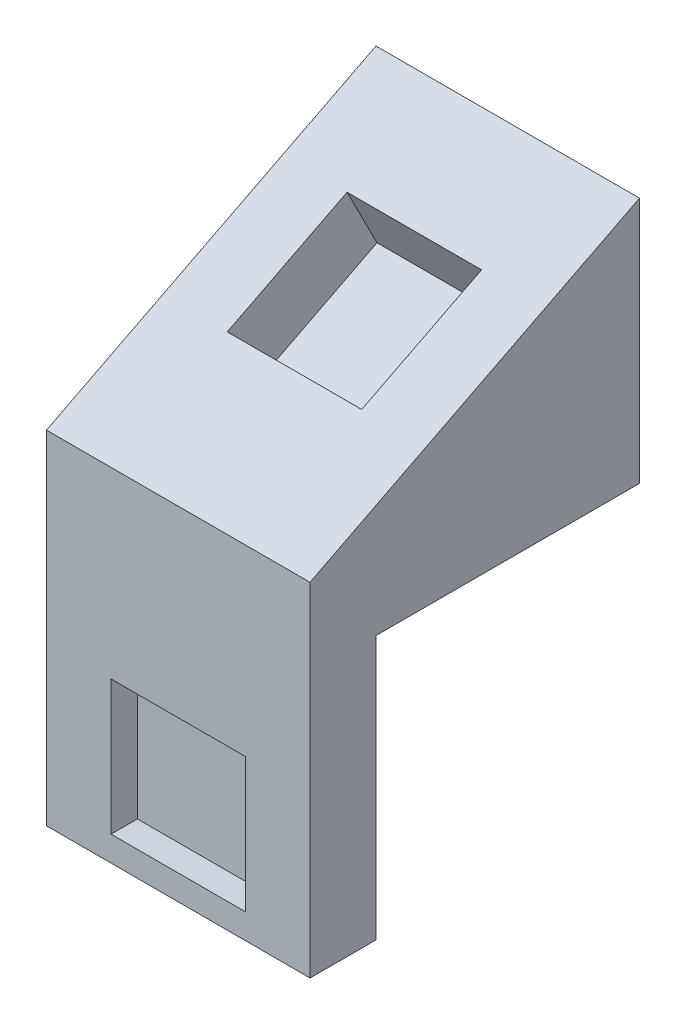
SolidWorks part; units mm, degrees
ref_plane "Płaszczyzna przednia" through (0, 0, 0) normal (0, 0, 1) x (1, 0, 0)
ref_plane "Płaszczyzna górna" through (0, 0, 0) normal (0, 1, 0) x (1, 0, 0)
ref_plane "Płaszczyzna prawa" through (0, 0, 0) normal (1, 0, 0) x (0, 0, -1)
sketch "Szkic1" plane through (0, 0, 0) normal (0, 0, 1) x (1, 0, 0)
  line L1 (-10, -13) -> (10, -13)
  line L2 (-10, -13) -> (-10, 13)
  line L3 (-10, 13) -> (10, 13)
  line L4 (10, -13) -> (10, 13)
  line L5 (-10, -13) -> (10, 13) construction
  line L6 (-10, 13) -> (10, -13) construction
  point P0 (0, 0)
  dimension "D1" = 26
  dimension "D2" = 20
extrude "Dodanie-wyciągnięcie1" add sketch "Szkic1" along normal blind 5
sketch "Szkic2" plane through (0, 0, 0) normal (0, 0, -1) x (-1, 0, 0)
  line L1 (10, 13) -> (-10, 13)
  line L2 (10, 13) -> (10, 7)
  line L3 (10, 7) -> (-10, 7)
  line L4 (-10, 13) -> (-10, 7)
  line L5 (-10, -13) -> (-10, 13) construction
  dimension "D1" = 6
  dimension "D2" = 20
extrude "Dodanie-wyciągnięcie2" add sketch "Szkic2" along normal blind 20
sketch "Szkic3" plane through (0, 0, 5) normal (0, 0, 1) x (1, 0, 0)
  line L0 (10, 13) -> (-10, 13) construction
  line L1 (-5.1, -11.1) -> (5.1, -11.1)
  line L2 (-5.1, -11.1) -> (-5.1, -0.9)
  line L3 (-5.1, -0.9) -> (5.1, -0.9)
  line L4 (5.1, -11.1) -> (5.1, -0.9)
  line L5 (-5.1, -11.1) -> (5.1, -0.9) construction
  line L6 (-5.1, -0.9) -> (5.1, -11.1) construction
  line L7 (-10, -13) -> (10, -13) construction
  point P0 (0, -6)
  point P7 (0, 13)
  dimension "D1" = 10.2
  dimension "D2" = 7
extrude "Wytnij-wyciągnięcie1" cut sketch "Szkic3" against normal blind 2
sketch "Szkic4" plane through (10, 0, 0) normal (1, 0, 0) x (0, 0, -1)
  line L0 (-5, 13) -> (20, 25.7381)
  line L1 (-5, 13) -> (20, 13) construction
  line L2 (20, 25.7381) -> (20, 13)
  line L3 (20, 13) -> (-5, 13)
  line L4 (-5, -13) -> (-5, 13) construction
  point P6 (-5, 13)
  point P7 (9.751, 22.2583)
  point P8 (0, 0)
  point P11 (20, 27.3975)
  dimension "D1" = 27
extrude "Dodanie-wyciągnięcie3" add sketch "Szkic4" against normal up to surface (20 mm away) up to face at (-10, 2.3333, -5)
sketch "Szkic5" plane through (0, 12.3431, 6.2891) normal (0, 0.891, 0.454) x (1, 0, 0)
  line L0 (10, 1.4468) -> (-10, 1.4468) construction
  line L1 (-5.1, 11.3468) -> (5.1, 11.3468)
  line L2 (-5.1, 11.3468) -> (-5.1, 21.5468)
  line L3 (-5.1, 21.5468) -> (5.1, 21.5468)
  line L4 (5.1, 11.3468) -> (5.1, 21.5468)
  line L5 (-5.1, 11.3468) -> (5.1, 21.5468) construction
  line L6 (-5.1, 21.5468) -> (5.1, 11.3468) construction
  point P0 (0, 16.4468)
  point P7 (0, 0)
  dimension "D1" = 10.2
  dimension "D2" = 15
extrude "Wytnij-wyciągnięcie2" cut sketch "Szkic5" against normal blind 5
